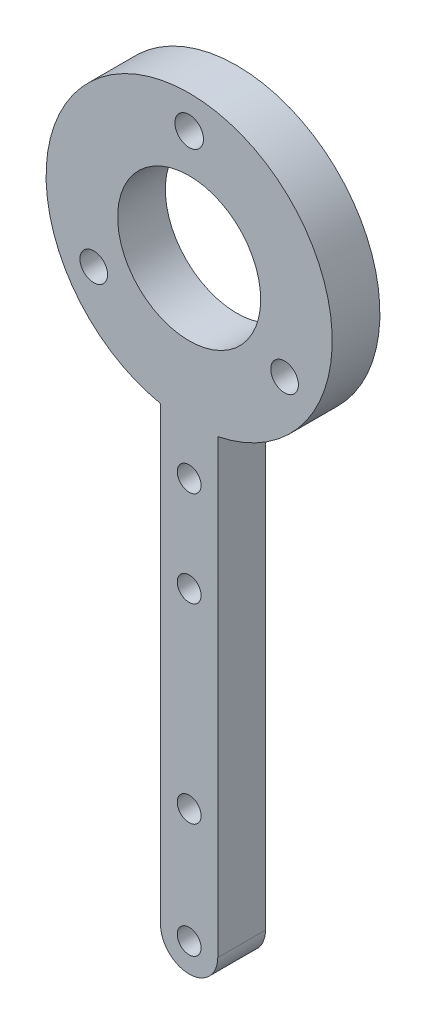
SolidWorks part; units mm, degrees
ref_plane "Plan de face" through (0, 0, 0) normal (0, 0, 1) x (1, 0, 0)
ref_plane "Plan de dessus" through (0, 0, 0) normal (0, 1, 0) x (1, 0, 0)
ref_plane "Plan de droite" through (0, 0, 0) normal (1, 0, 0) x (0, 0, -1)
sketch "Esquisse1" plane through (0, 0, 0) normal (0, 0, 1) x (1, 0, 0)
  line L0 (0, -15) -> (0, -65) construction
  line L1 (3, -14.6969) -> (3, -65)
  line L2 (-3, -14.6969) -> (-3, -65)
  line L3 (3, -65) -> (-3, -65)
  circle A0 centre (0, 0) radius 15
  circle A1 centre (0, 0) radius 7.5
  circle A2 centre (-10.0026, -5.775) radius 1.45
  circle A3 centre (0, 11.55) radius 1.4988
  circle A4 centre (10.0026, -5.775) radius 1.45
  dimension "D1" = 15
  dimension "D2" = 30
  dimension "D3" = 3
  dimension "D4" = 3
  dimension "D5" = 50
extrude "Boss.-Extru.1" add sketch "Esquisse1" along normal blind 5 contours A0 L0 L3 L1 | L0 A0 L2 L3 | A0 A4 A3 A2 A1 region at (1.5015, -39.9496, 0) region at (-1.5015, -39.9496, 0) region at (-1.465, -14.5019, 0)
fillet "Congé1" radius 3 1 edges at (3, -65, 2.5)
fillet "Congé2" radius 3 1 edges at (-3, -65, 2.5)
sketch "Esquisse2" plane through (0, 0, 5) normal (0, 0, 1) x (1, 0, 0)
  circle A0 centre (0, -20) radius 1.25
  circle A1 centre (0, -30) radius 1.25
  circle A2 centre (0, -50) radius 1.25
  circle A3 centre (0, -62) radius 1.25
  dimension "D1" = 2.5
  dimension "D2" = 2.5
  dimension "D3" = 2.5
  dimension "D4" = 2.5
  dimension "D5" = 20
  dimension "D6" = 30
  dimension "D7" = 50
  dimension "D8" = 62
extrude "Enlèv. mat.-Extru.1" cut sketch "Esquisse2" against normal up to next
